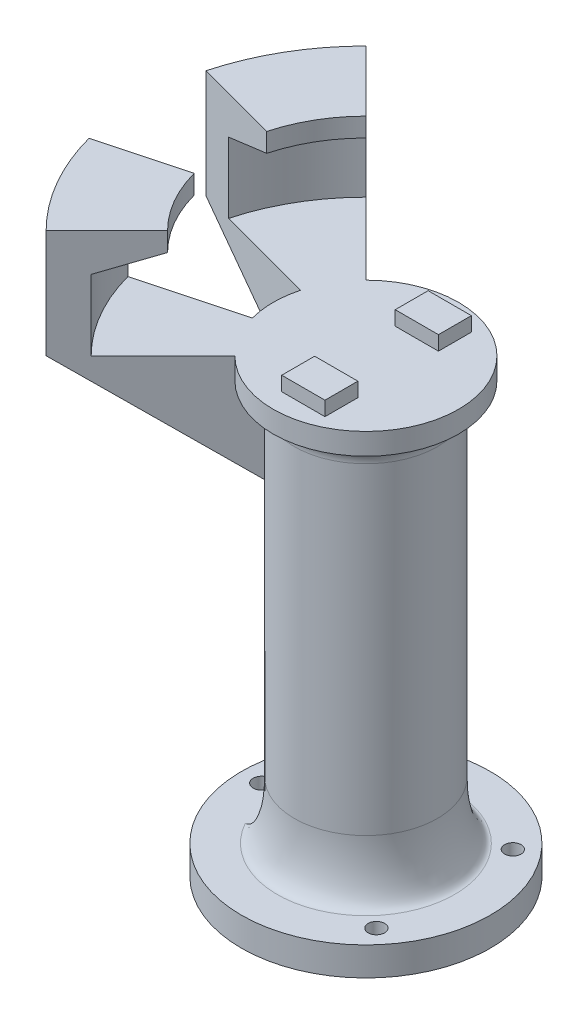
SolidWorks part; units mm, degrees
ref_plane "Front Plane" through (0, 0, 0) normal (0, 0, 1) x (1, 0, 0)
ref_plane "Top Plane" through (0, 0, 0) normal (0, 1, 0) x (1, 0, 0)
ref_plane "Right Plane" through (0, 0, 0) normal (1, 0, 0) x (0, 0, -1)
sketch "Sketch1" plane through (0, 0, 0) normal (0, 1, 0) x (1, 0, 0)
  circle A0 centre (0, 0) radius 22.098
  circle A1 centre (0, 0) radius 9.525
  dimension "D1" = 44.196
  dimension "D2" = 19.05
extrude "Boss-Extrude1" add sketch "Sketch1" along normal blind 5.08 contours A1 | A0 A1 region at (-21.473, 0, 0) region at (0, 0, 0)
sketch "Sketch4" plane through (0, 5.08, 0) normal (0, 1, 0) x (1, 0, 0)
  line L1 (0, 0) -> (59.9509, 0)
  line L2 (0, 0) -> (22.476, 19.4807)
  line L3 (11.238, 9.7404) -> (16.6987, 14.4733)
  circle A1 centre (0, 0) radius 22.098 construction
  circle A3 centre (13.9683, 12.1068) radius 1.4605
  circle A4 centre (13.9683, -12.1068) radius 1.4605
  circle A5 centre (-18.4849, 0) radius 1.524
  dimension "D1" = 18.4849
  dimension "D3" = 2.921
  dimension "D4" = 2.921
  dimension "D6" = 3.048
  dimension "D2" = 40.917
  dimension "D5" = 18.4849
extrude "Cut-Extrude1" cut sketch "Sketch4" against normal blind 58.42 contours A3 | A4 | A5
sketch "Sketch5" plane through (0, 0, 0) normal (0, -1, 0) x (1, 0, 0)
  circle A0 centre (0, 0) radius 12.7
  dimension "D1" = 25.4
extrude "Cut-Extrude2" cut sketch "Sketch5" against normal blind 29.21
extrude "Boss-Extrude2" add sketch "Sketch5<3>" against normal blind 76.2 contours A0
sketch "Sketch5<3>" plane through (0, 0, 0) normal (0, -1, 0) x (1, 0, 0) same geometry as "Sketch5"
sketch "Sketch6" plane through (0, 0, 0) normal (0, -1, 0) x (1, 0, 0)
  circle A0 centre (0, 0) radius 7.62
  dimension "D1" = 15.24
extrude "Cut-Extrude3" cut sketch "Sketch6" against normal blind 17.78
sketch "Sketch7" plane through (0, 0, 0) normal (1, 0, 0) x (0, 0, -1)
  line L0 (0, 0) -> (0, 12.7)
  line L1 (-22.098, 5.08) -> (-22.098, 0)
  line L7 (-7.62, 0) -> (7.62, 0)
  line L8 (-7.62, 0) -> (-7.62, 13.637)
  line L9 (-5.08, 16.177) -> (5.08, 16.177)
  line L10 (7.62, 0) -> (7.62, 13.637)
  line L11 (-7.62, 16.177) -> (7.62, 16.177)
  line L12 (-7.62, 16.177) -> (-7.62, 5.08)
  line L13 (-7.62, 5.08) -> (7.62, 5.08)
  line L14 (7.62, 16.177) -> (7.62, 5.08)
  arc A4 (7.62, 13.637) -> (5.08, 16.177) centre (5.08, 13.637) ccw
  arc A5 (-7.62, 13.637) -> (-5.08, 16.177) centre (-5.08, 13.637) cw
  point P20 (4.4443, 5.08)
  point P23 (4.4443, 12.7)
  dimension "D4" = 2.54
  dimension "D1" = 12.7
  dimension "D2" = 5.08
  dimension "D3" = 7.62
extrude "Cut-Extrude4" cut sketch "Sketch7" against normal through all contours L12 L13 L14 L11
sketch "Sketch8" plane through (0, 76.2, 0) normal (0, 1, 0) x (1, 0, 0)
  line L0 (0, 0) -> (-7.8176, 0)
  line L1 (-1.9467, 7.1501) -> (5.7241, 7.1501)
  line L2 (-1.9467, 7.1501) -> (-1.9467, 12.9921)
  line L3 (-1.9467, 12.9921) -> (5.7241, 12.9921)
  line L4 (5.7241, 7.1501) -> (5.7241, 12.9921)
  line L5 (-1.9467, -12.9921) -> (5.7241, -12.9921)
  line L6 (5.7241, -7.1501) -> (5.7241, -12.9921)
  line L7 (-1.9467, -7.1501) -> (5.7241, -7.1501)
  line L8 (-1.9467, -7.1501) -> (-1.9467, -12.9921)
  circle A0 centre (0, 0) radius 16.4465
  circle M8 centre (0, 0) radius 12.7
  dimension "D1" = 32.893
  dimension "D2" = 5.842
  dimension "D3" = 7.6708
  dimension "D4" = 14.3002
extrude "Boss-Extrude3" add sketch "Sketch8" along normal blind 3.81 contours A0 L8 L2 L3 L4 L6 L5 M8 | L8 L5 L6 M8 | L4 L3 L2 M8 | L8 L7 L6 L4 L1 L2 | L1 L4 L2 M8 | L7 L8 L6 M8 region at (1.7428, 76.2, -9.7675) region at (1.8887, 76.2, -6.793) region at (3.0829, 76.2, -12.5552) region at (3.0829, 76.2, 12.5552) region at (1.7428, 76.2, 9.7675) region at (-15.9813, 76.2, 0)
extrude "Boss-Extrude4" add sketch "Sketch8<3>" along normal blind 6.35 contours L7 L6 L5 L8 | L1 L4 L3 L2
sketch "Sketch8<3>" plane through (0, 76.2, 0) normal (0, 1, 0) x (1, 0, 0) same geometry as "Sketch8"
sketch "Sketch9" plane through (0, 80.01, 0) normal (0, 1, 0) x (1, 0, 0)
  line L0 (0, 0) -> (-24.3814, 24.3814)
  line L1 (0, 0) -> (0, 24.3804)
  line L2 (0, 0) -> (-24.3814, -24.3814)
  line L3 (0, 0) -> (-28.3776, -28.3776)
  line L4 (-24.3814, 24.3814) -> (-28.3776, 28.3776)
  circle A0 centre (0, 0) radius 34.4805
  arc A1 (-20.7012, 27.5747) -> (-20.7012, -27.5747) centre (0, 0) cw
  arc A2 (-24.3814, 24.3814) -> (-24.3814, -24.3814) centre (0, 0) cw
  arc A3 (-28.3776, -28.3776) -> (-28.3776, 28.3776) centre (0, 0) cw
  arc A4 (-24.3814, -24.3814) -> (-24.3814, 24.3814) centre (0, 0) cw
  circle M11 centre (0, 0) radius 16.4465
  dimension "D1" = 68.961
  dimension "D2" = 45
  dimension "D3" = 40.132
extrude "Boss-Extrude5" add sketch "Sketch9" along normal blind 15.875 separate body contours A3 L3 A0 L4 region at (-35.0695, 80.01, 0)
sketch "Sketch10" plane through (0, 95.885, 0) normal (0, 1, 0) x (1, 0, 0)
  line L0 (-28.3776, -28.3776) -> (-17.6013, -17.6013)
  line L1 (-28.3776, 28.3776) -> (-17.6013, 17.6013)
  circle A1 centre (0, 0) radius 40.132
  arc A2 (-17.6013, 17.6013) -> (-17.6013, -17.6013) centre (0, 0) ccw
  arc A3 (-28.3776, -28.3776) -> (-28.3776, 28.3776) centre (0, 0) cw
  arc A4 (-17.6013, -17.6013) -> (-17.6013, 17.6013) centre (0, 0) cw
  arc M5 (-28.3776, 28.3776) -> (-28.3776, -28.3776) centre (0, 0) ccw
  line M6 (-28.3776, -28.3776) -> (-24.3814, -24.3814)
  arc M7 (-24.3814, -24.3814) -> (-24.3814, 24.3814) centre (0, 0) cw
  line M8 (-24.3814, 24.3814) -> (-28.3776, 28.3776)
  dimension "D1" = 15.24
  dimension "D2" = 15.24
extrude "Boss-Extrude6" add sketch "Sketch10" along normal mid plane 6.731 contours A2 L1 L0 M7 | M8 M5 M6 M7 region at (-39.543, 95.885, 0) region at (-26.9594, 95.885, 0)
sketch "Sketch11" plane through (0, 0, 0) normal (0.7071, 0, 0.7071) x (0.7071, 0, -0.7071)
  line L0 (-34.4805, 92.5195) -> (-24.892, 95.885)
  line L1 (-24.892, 99.2505) -> (-24.892, 92.5195) construction
  line L2 (-24.892, 95.885) -> (-24.892, 92.5195)
  line L3 (-24.892, 92.5195) -> (-34.4805, 92.5195)
sketch "Sketch12" plane through (0, 0, 0) normal (1, 0, 0) x (0, 0, -1)
  line L0 (0, 80.01) -> (0, 88.2378)
  line L1 (-24.3814, 80.01) -> (24.3814, 80.01) construction
revolve "Cut-Revolve3" cut sketch "Sketch11" angle 360 about L0
extrude "Boss-Extrude7" add sketch "Sketch9<5>" against normal blind 19.05 contours L0 A0 L2 M11 | A3 L3 A0 L4 | L2 L0 M11 region at (-9.8714, 80.01, 0) region at (-23.8835, 80.01, 0) region at (-35.0695, 80.01, 0)
sketch "Sketch9<5>" plane through (0, 80.01, 0) normal (0, 1, 0) x (1, 0, 0) same geometry as "Sketch9"
sketch "Sketch14" plane through (0, 0, 0) normal (0.7071, 0, 0.7071) x (0.7071, 0, -0.7071)
  line L0 (-12.7, 60.96) -> (-40.132, 80.01)
  line L1 (0, 80.01) -> (-40.132, 80.01) construction
  line L2 (0, 80.01) -> (-40.132, 80.01) construction
  line L3 (-40.132, 80.01) -> (-40.132, 60.96)
  line L4 (-40.132, 60.96) -> (-12.7, 60.96)
revolve "Cut-Revolve4" cut sketch "Sketch14" about L0 reverse direction yes
sketch "Sketch15" plane through (0, 80.01, 0) normal (0, 1, 0) x (1, 0, 0)
  line L0 (0, 0) -> (-38.7645, 10.3869)
  line L1 (0, 0) -> (-24.3814, 24.3814) construction
  line L2 (0, 0) -> (-38.7645, -10.3869)
  arc A0 (-28.3776, 28.3776) -> (-28.3776, -28.3776) centre (0, 0) ccw construction
  arc A1 (-38.7645, 10.3869) -> (-38.7645, -10.3869) centre (0, 0) ccw
  circle A2 centre (0, 0) radius 16.4465
  arc M2 (-24.3814, 24.3814) -> (-24.3814, -24.3814) centre (0, 0) ccw
  dimension "D1" = 30
extrude "Cut-Extrude5" cut sketch "Sketch15" along normal mid plane 139.7 contours L2 L0 M2 | L0 A1 L2 M2 region at (-26.2259, 80.01, 0) region at (-36.9521, 80.01, 0)
fillet "Fillet1" radius 3.048 1 edges at (12.7, 5.08, 0) second distance 10.16 first distance on face at (-1.27, 5.08, 0)
fillet "Fillet2" radius 3.81 1 edges at (12.7, 76.2, 0)
